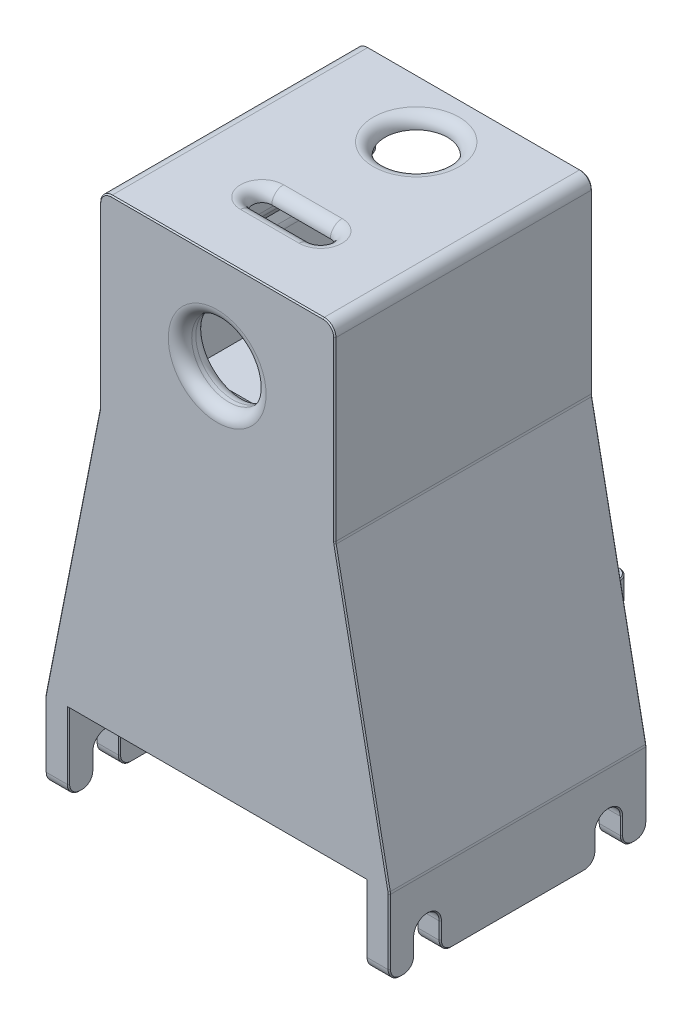
SolidWorks part; units mm, degrees
note: The reader was unsure of these and kept them because the rebuilt part matched: shared geometry of "base_sketch<3>", "base_sketch<4>", "Sketch2<3>", "Sketch2<4>".
other "small"
ref_plane "Front Plane" through (0, 0, 0) normal (0, 0, 1) x (1, 0, 0)
ref_plane "Top Plane" through (0, 0, 0) normal (0, 1, 0) x (1, 0, 0)
ref_plane "Right Plane" through (0, 0, 0) normal (1, 0, 0) x (0, 0, -1)
sketch "top_sketch" plane through (0, 0, 0) normal (0, 0, 1) x (1, 0, 0)
  line L0 (-30.1363, 21.25) -> (30.1363, 21.25)
  line L1 (-30.1363, 24.25) -> (30.1363, 24.25)
  line L2 (-30.1363, 24.25) -> (-30.1363, -24.25)
  line L3 (-30.1363, -24.25) -> (30.1363, -24.25)
  line L4 (30.1363, 24.25) -> (30.1363, -24.25)
  line L5 (12.9462, 21.25) -> (-12.9462, 21.25) construction
  line L6 (-30.1363, -21.25) -> (30.1363, -21.25)
  line L7 (12.9462, -21.25) -> (-12.9462, -21.25) construction
  line L8 (-25.1194, -2.4927) -> (-24.1363, -21.25)
  line L9 (-25.25, 0) -> (-24.722, -10.0752) construction
  line L10 (-25.1437, 2.5073) -> (-24.0994, 21.25)
  line L11 (-24.7199, 10.1141) -> (-25.25, 0.6) construction
  line L12 (0, 21.25) -> (0, -21.25) construction
  line L13 (12.9462, -21.25) -> (-12.9462, -21.25) construction
  line L14 (-30.1363, 0) -> (30.1363, 0) construction
  line L15 (-25.1437, 2.5073) -> (-26.6363, 0)
  line L16 (-26.6363, 0) -> (-25.1194, -2.4927)
  line L17 (25.1194, -2.4927) -> (24.1363, -21.25)
  line L18 (26.6363, 0) -> (25.1194, -2.4927)
  line L19 (25.1437, 2.5073) -> (26.6363, 0)
  line L20 (25.1437, 2.5073) -> (24.0994, 21.25)
  line L21 (12.9462, 19.65) -> (-12.9462, 19.65) construction
  line L22 (6.85, 13.65) -> (-6.85, 13.65)
  line L23 (16.85, 3.65) -> (16.85, -3.65)
  line L24 (6.85, -13.65) -> (-6.85, -13.65)
  line L25 (-16.85, 3.65) -> (-16.85, -3.65)
  line L26 (0, -13.65) -> (0, 13.65) construction
  line L27 (16.85, 0) -> (-16.85, 0) construction
  line L28 (22.85, -1.6) -> (22.85, 2.2) construction
  arc A0 (6.85, 13.65) -> (16.85, 3.65) centre (6.85, 3.65) cw
  arc A1 (16.85, -3.65) -> (6.85, -13.65) centre (6.85, -3.65) cw
  arc A2 (-6.85, -13.65) -> (-16.85, -3.65) centre (-6.85, -3.65) cw
  arc A3 (-6.85, 13.65) -> (-16.85, 3.65) centre (-6.85, 3.65) ccw
  circle A4 centre (0, 0) radius 9.525
  point P39 (0, 0)
  dimension "D5" = 10
  dimension "D8" = 19.05
  dimension "D1" = 3
  dimension "D2" = 6
  dimension "D3" = 3.5
  dimension "D4" = 5
  dimension "D6" = 6
  dimension "D7" = 6
extrude "lamp_base" add sketch "top_sketch" along normal blind 6 contours L16 L15 L10 L0 L2 L6 L8 | L4 L1 L2 L0 | L19 L20 L0 L10 L15 L16 L8 L6 L17 L18 A3 L22 A0 L23 A1 L24 A2 L25 | L20 L19 L18 L17 L6 L4 L0 | L6 L2 L3 L4 | L22 A3 L25 A2 L24 A1 L23 A0 A4
extrude "lamp_base_boss" add sketch "base_sketch<3>" against normal up to body (1.05 mm away) separate body contours L22 A3 L25 A2 L24 A1 L23 A0
sketch "base_sketch<3>" plane through (0, 0, 0) normal (0, 0, 1) x (1, 0, 0) same geometry as "top_sketch"
extrude "walls" add sketch "base_sketch<4>" against normal blind 60 separate body contours L16 L15 L10 L0 L2 L6 L8 | L6 L2 L3 L4 | L20 L19 L18 L17 L6 L4 L0 | L4 L1 L2 L0
sketch "base_sketch<4>" plane through (0, 0, 0) normal (0, 0, 1) x (1, 0, 0) same geometry as "top_sketch"
sketch "ui_cutout_sketch" plane through (0, 24.25, 0) normal (0, 1, 0) x (1, 0, 0)
  line L0 (0, 0) -> (0, 45) construction
  line L1 (7.5, 13) -> (-7.5, 13) construction
  line L2 (7.5, 10.5) -> (-7.5, 10.5)
  line L3 (7.5, 15.5) -> (-7.5, 15.5)
  circle A0 centre (0, 45) radius 8
  arc A1 (7.5, 10.5) -> (7.5, 15.5) centre (7.5, 13) ccw
  arc A2 (-7.5, 15.5) -> (-7.5, 10.5) centre (-7.5, 13) ccw
  point P6 (0, 13)
  dimension "D1" = 16
  dimension "D2" = 45
  dimension "D3" = 13
  dimension "D4" = 5
  dimension "D5" = 15
extrude "ui_cutout" cut sketch "ui_cutout_sketch" against normal up to next
sketch "vent_cutout_sketch" plane through (0, -24.25, 0) normal (0, -1, 0) x (1, 0, 0)
  line L0 (0, 0) -> (0, -7.5) construction
  line L1 (-14, -7.5) -> (14, -7.5) construction
  line L2 (-14, -3.5) -> (14, -3.5)
  line L3 (-14, -11.5) -> (14, -11.5)
  arc A0 (-14, -3.5) -> (-14, -11.5) centre (-14, -7.5) ccw
  arc A1 (14, -11.5) -> (14, -3.5) centre (14, -7.5) ccw
  point P5 (0, -7.5)
  dimension "D1" = 7.5
  dimension "D2" = 8
  dimension "D3" = 28
extrude "vent_cutout" cut sketch "vent_cutout_sketch" against normal up to next
sketch "base_sketch" plane through (0, 0, 6) normal (0, 0, 1) x (1, 0, 0)
  line L0 (-38.1, -115.007) -> (-44.1, -115.007)
  line L1 (-38.1, -115.007) -> (-38.1, -95.007)
  line L2 (-38.1, -103.5166) -> (-38.1, -102.4634) construction
  line L3 (-38.1, -95.007) -> (38.1, -95.007)
  line L4 (-35.2037, -95.007) -> (-31.7485, -95.007) construction
  line L5 (-14.4914, -95.007) -> (-10.9086, -95.007) construction
  line L6 (-44.1, -115.007) -> (-44.1, -95.007)
  line L7 (-44.1, -95.007) -> (-30.1363, -24.25)
  line L8 (30.1363, -24.25) -> (-30.1363, -24.25)
  line L10 (0, -24.25) -> (0, -95.007) construction
  line L11 (44.1, -95.007) -> (30.1363, -24.25)
  line L12 (44.1, -115.007) -> (44.1, -95.007)
  line L13 (38.1, -115.007) -> (44.1, -115.007)
  line L14 (38.1, -115.007) -> (38.1, -95.007)
  line L15 (-42.9159, -89.007) -> (42.9159, -89.007)
  line L16 (-38.1, -95.007) -> (-36.9159, -89.007) construction
  line L17 (-36.9159, -89.007) -> (-24.1363, -24.25)
  line L18 (-38.1, -95.007) -> (-38.1, -89.007) construction
  line L19 (36.9159, -89.007) -> (24.1363, -24.25)
  line L20 (-10, -95.007) -> (-10, -89.007)
  line L21 (10, -95.007) -> (10, -89.007)
  line L22 (-30.1363, -24.25) -> (30.1363, -24.25) construction
  dimension "D1" = 6
  dimension "D2" = 20
  dimension "D3" = 20
extrude "Boss-Extrude1" add sketch "base_sketch" against normal blind 6
extrude "Boss-Extrude2" add sketch "Sketch2<3>" against normal up to surface (66 mm away) up to face at (0, 0, -60)
sketch "Sketch2<3>" plane through (0, 0, 6) normal (0, 0, 1) x (1, 0, 0) same geometry as "base_sketch"
extrude "alignment_tab" add sketch "Sketch2<4>" against normal blind 30 from surface contours L3 L21 L15 L20
sketch "Sketch2<4>" plane through (0, 0, 6) normal (0, 0, 1) x (1, 0, 0) same geometry as "base_sketch"
sketch "alignment_peg_sketch" plane through (0, -95.007, 0) normal (0, -1, 0) x (1, 0, 0)
  circle A0 centre (0, -79.7) radius 3.2639
  circle A1 centre (0, -79.7) radius 3.2639 construction
  dimension "D1" = 6.5278
extrude "alignment_peg" add sketch "alignment_peg_sketch" along normal blind 19.05
sketch "mounting_slots_sketch" plane through (44.1, 0, 0) normal (1, 0, 0) x (0, 0, -1)
  line L0 (0.5278, -115.007) -> (0.5278, -107.707)
  line L1 (60, -115.007) -> (-6, -115.007) construction
  line L2 (7.0556, -115.007) -> (7.0556, -107.707)
  line L3 (0.5278, -115.007) -> (7.0556, -115.007)
  line L4 (-47.3, -107.707) -> (3.7917, -107.707) construction
  line L5 (-47.3, -105.543) -> (-47.3, -109.871) construction
  line L6 (0.5278, -111.357) -> (-6, -111.357) construction
  line L7 (-6, -115.007) -> (-6, -95.007) construction
  line L8 (27, -95.007) -> (27, -115.007) construction
  line L9 (60, -95.007) -> (-6, -95.007) construction
  line L10 (53.4722, -115.007) -> (53.4722, -107.707)
  line L11 (53.4722, -115.007) -> (46.9444, -115.007)
  line L12 (46.9444, -115.007) -> (46.9444, -107.707)
  arc A0 (0.5278, -107.707) -> (7.0556, -107.707) centre (3.7917, -107.707) cw
  arc A1 (53.4722, -107.707) -> (46.9444, -107.707) centre (50.2083, -107.707) ccw
  dimension "D1" = 6.5278
extrude "mounting_slots" cut sketch "mounting_slots_sketch" against normal through all
fillet "large_roundover" radius 3 52 edges at (-14, -22.75, -11.5) (-14, -22.75, -3.5) (14, -22.75, -3.5) (14, -22.75, -11.5) (-18, -24.25, -7.5) (0, -24.25, -11.5) (18, -24.25, -7.5) (0, -24.25, -3.5) (30.1363, -24.25, -27) (-30.1363, -24.25, -27) (-30.1363, 24.25, -27) (44.1, -95.007, -27) (30.1363, 24.25, -27) (-41.1, -115.007, 6) (-44.1, -95.007, -27) (41.1, -115.007, 6) (-30.5261, -56.6285, 0) (0, -89.007, 0) (30.5261, -56.6285, 0) (-41.1, -115.007, -60) (24.1363, -24.25, -30) (36.9159, -89.007, -30) (-36.9159, -89.007, -30) (-24.1363, -24.25, -30) (41.1, -115.007, -60) (-10, -92.007, -60) (10, -92.007, -90) (-10, -92.007, -90) (10, -92.007, -60) (41.1, -115.007, -7.0556) (41.1, -115.007, -0.5278) (-41.1, -115.007, -7.0556) (-41.1, -115.007, -0.5278) (-9.525, 0, -1.05) (41.1, -115.007, -53.4722) (41.1, -115.007, -46.9444) (-41.1, -115.007, -53.4722) (-41.1, -115.007, -46.9444) (9.525, 0, 6) (-25.1194, -2.4927, -30) (25.1194, -2.4927, -30) (25.1437, 2.5073, -30) (-25.1437, 2.5073, -30) (0, 24.25, -37) (10, 24.25, -13) (0, 24.25, -15.5) (-10, 24.25, -13) (0, 24.25, -10.5) (-7.5, 22.75, -15.5) (-7.5, 22.75, -10.5) (7.5, 22.75, -10.5) (7.5, 22.75, -15.5)
chamfer "Chamfer1" distance 0.3 angle 45 139 edges at (0, -95.007, 6) (38.1, -103.507, -60) (25.55, -95.007, -60) (-38.1, -103.507, -60) (0, -114.057, -82.9639) (38.1, -109.857, -0.5278) (-38.1, -109.857, -0.5278) (38.1, -104.4431, -3.7917) (-38.1, -104.4431, -3.7917) (-44.1, -109.857, -0.5278) (-44.1, -104.4431, -3.7917) (44.1, -104.4431, -3.7917) (44.1, -109.857, -0.5278) (13.9211, 10.7211, -1.05) (16.85, 0, -1.05) (13.9211, -10.7211, -1.05) (0, -13.65, -1.05) (-13.9211, -10.7211, -1.05) (38.1, -104.4431, -50.2083) (-38.1, -104.4431, -50.2083) (-13.9211, 10.7211, -1.05) (38.1, -109.857, -46.9444) (-38.1, -109.857, -46.9444) (-44.1, -104.4431, -50.2083) (-44.1, -109.857, -46.9444) (-16.85, 0, -1.05) (44.1, -104.4431, -50.2083) (44.1, -109.857, -46.9444) (0, 13.65, -1.05) (0, -24.25, -60) (0, 24.25, -60) (0, 24.25, 6) (37.1182, -59.6285, 6) (30.1363, -1.3534, 6) (-30.1363, -1.3534, 6) (-37.1182, -59.6285, 6) (-44.1, -103.6536, 6) (-38.1, -103.507, 6) (38.1, -103.507, 6) (44.1, -103.6536, 6) (29.2577, 23.3713, 6) (-29.2577, 23.3713, 6) (-44.0858, -95.0084, 6) (44.0858, -95.0084, 6) (-38.1, -115.007, -56.7361) (-44.1, -115.007, -56.7361) (-38.1, -109.857, -7.0556) (-38.1, -115.007, -27) (-38.1, -109.857, -53.4722) (-38.1, -115.007, 2.7361) (-38.1, -114.1283, 5.1213) (-38.1, -114.1283, 0.3509) (-38.1, -114.1283, -7.9343) (-38.1, -114.1283, -46.0657) (-38.1, -114.1283, -54.3509) (-38.1, -114.1283, -59.1213) (-24.608, -12.2493, -60) (24.608, -12.2493, -60) (26.0783, 0.9374, -60) (24.6011, 12.2462, -60) (-24.6011, 12.2462, -60) (-26.0783, 0.9374, -60) (-25.55, -95.007, -60) (-44.1, -103.6536, -60) (-37.1182, -59.6285, -60) (-30.1363, -1.3534, -60) (30.1363, -1.3534, -60) (37.1182, -59.6285, -60) (44.1, -103.6536, -60) (23.133, -89.007, -60) (30.4115, -56.0477, -60) (-30.4115, -56.0477, -60) (-23.133, -89.007, -60) (29.2577, 23.3713, -60) (-29.2577, 23.3713, -60) (25.2289, 2.5333, -60) (25.2092, -2.5204, -60) (-25.2092, -2.5204, -60) (-25.2289, 2.5333, -60) (-44.0858, -95.0084, -60) (44.0858, -95.0084, -60) (-44.1, -115.007, 2.7361) (-44.1, -109.857, -53.4722) (-44.1, -115.007, -27) (-44.1, -109.857, -7.0556) (-44.1, -114.1283, 5.1213) (-44.1, -114.1283, 0.3509) (-44.1, -114.1283, -7.9343) (-44.1, -114.1283, -46.0657) (-44.1, -114.1283, -54.3509) (-44.1, -114.1283, -59.1213) (44.1, -109.857, -7.0556) (38.1, -109.857, -7.0556) (44.1, -115.007, -27) (44.1, -109.857, -53.4722) (44.1, -115.007, -56.7361) (44.1, -115.007, 2.7361) (44.1, -114.1283, -46.0657) (44.1, -114.1283, -54.3509) (44.1, -114.1283, -59.1213) (44.1, -114.1283, 5.1213) (44.1, -114.1283, 0.3509) (44.1, -114.1283, -7.9343) (38.1, -115.007, -27) (38.1, -115.007, 2.7361) (38.1, -115.007, -56.7361) (38.1, -109.857, -53.4722) (38.1, -114.1283, -46.0657) (38.1, -114.1283, -54.3509) (38.1, -114.1283, -59.1213) (38.1, -114.1283, 5.1213) (38.1, -114.1283, 0.3509) (38.1, -114.1283, -7.9343) (0, -89.007, -90) (0, -95.007, -90) (10, -89.007, -75) (-10, -89.007, -75) (9.1213, -89.007, -89.1213) (-9.1213, -89.007, -89.1213) (-10, -95.007, -75) (10, -95.007, -75) (9.1213, -95.007, -89.1213) (-9.1213, -95.007, -89.1213) (-23.5754, -24.9324, -60) (-10.8787, -89.007, -60.8787) (-10.8787, -95.007, -60.8787) (23.5754, -24.9324, -60) (10.8787, -89.007, -60.8787) (10.8787, -95.007, -60.8787) (35.5836, -87.9119, -60) (-35.5836, -87.9119, -60) (-30.1506, -24.2486, -60) (-30.1506, -24.2486, 6) (30.1506, -24.2486, -60) (30.1506, -24.2486, 6) (26.0746, -0.923, -60) (0, 21.25, -60) (-26.0746, -0.923, -60) (0, -21.25, -60)
